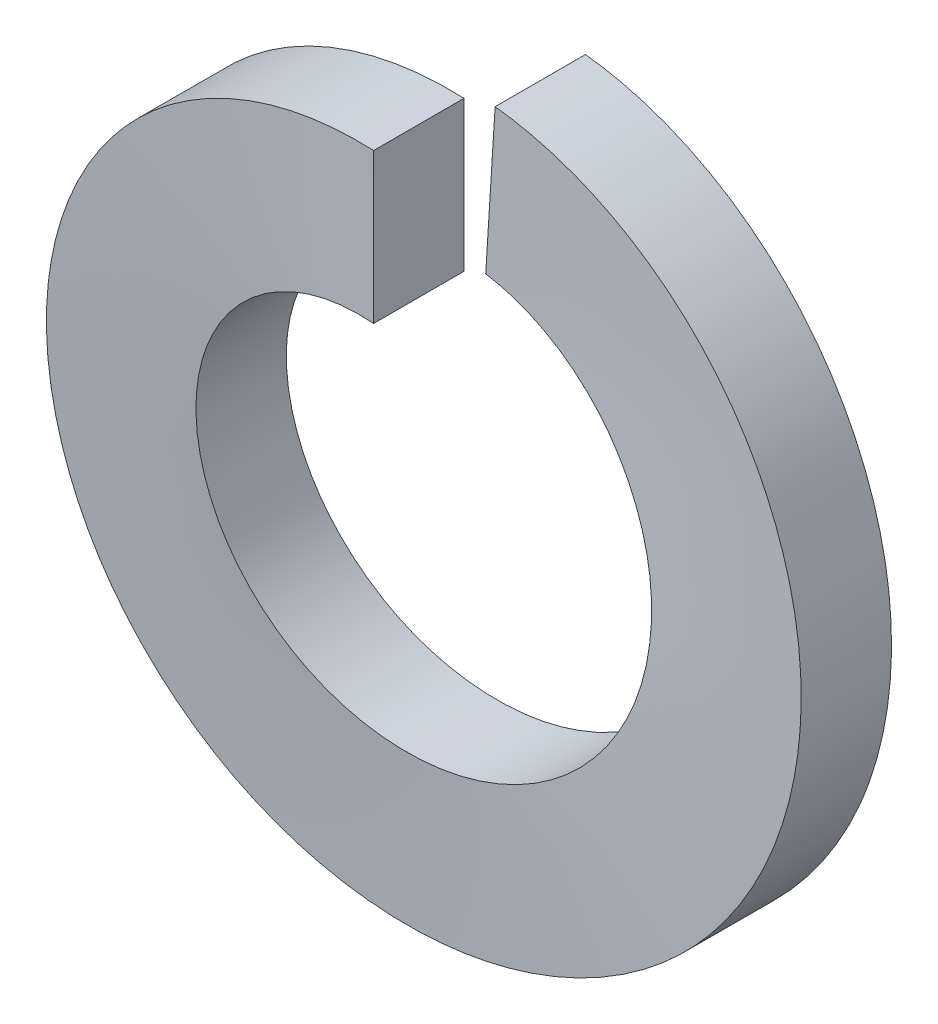
SolidWorks part; units mm, degrees
ref_plane "Front Plane" through (0, 0, 0) normal (0, 0, 1) x (1, 0, 0)
ref_plane "Top Plane" through (0, 0, 0) normal (0, 1, 0) x (1, 0, 0)
ref_plane "Right Plane" through (0, 0, 0) normal (1, 0, 0) x (0, 0, -1)
sketch "Sketch1" plane through (0, 0, 0) normal (0, 0, 1) x (1, 0, 0)
  line L0 (0, 7.4) -> (0, 4.25) construction
  circle A0 centre (0, 0) radius 7.4
  circle A1 centre (0, 0) radius 4.25 construction
  dimension "ID" = 8.5
  dimension "OD" = 14.8
curve "Helix/Spiral1" pitch 2.1111 height 2.09 radius 7.4 left hand yes centre (0, 0, 0) axis (0, 0, -1) start towards (0, 1, 0) parameters "HT"=2.09
sketch "Sketch2" plane through (0, 0, 0) normal (1, 0, 0) x (0, 0, -1)
  line L1 (0, 7.4) -> (-1.9, 7.4)
  line L2 (0, 7.4) -> (0, 4.25)
  line L3 (0, 4.25) -> (-1.9, 4.25)
  line L4 (-1.9, 7.4) -> (-1.9, 4.25)
  dimension "THK" = 1.9
sweep "Sweep1" add profiles "Sketch2" path "Helix/Spiral1"
ref_axis "Axis1" through (0, 0, -2.2957) along (0, 0, 1)
equation "\"HT@Helix/Spiral1\" = \"THK@Sketch2\"*1.1"
